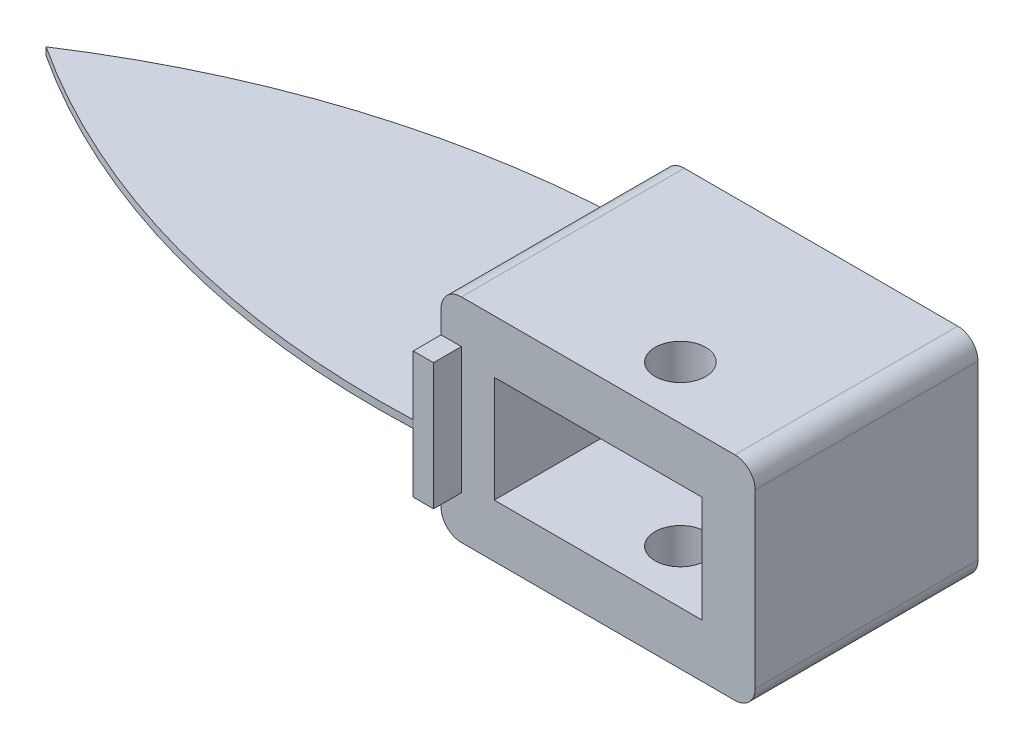
SolidWorks part; units mm, degrees
note: The reader was unsure of these and kept them because the rebuilt part matched: shared geometry of "草圖2<3>", "Sketch2<3>", "草圖5<3>".
ref_plane "前基準面" through (0, 0, 0) normal (0, 0, 1) x (1, 0, 0)
ref_plane "上基準面" through (0, 0, 0) normal (0, 1, 0) x (1, 0, 0)
ref_plane "右基準面" through (0, 0, 0) normal (1, 0, 0) x (0, 0, -1)
sketch "Sketch1" plane through (0, 0, 0) normal (0, 0, 1) x (1, 0, 0)
  line L0 (-29.0958, -4.1361) -> (32.9042, -4.1361) construction
  line L1 (-18.5958, 6.3639) -> (22.4042, 6.3639)
  line L2 (-18.5958, 6.3639) -> (-18.5958, -14.6361)
  line L3 (-18.5958, -14.6361) -> (22.4042, -14.6361)
  line L4 (22.4042, 6.3639) -> (22.4042, -14.6361)
  line L5 (-29.0958, 16.8639) -> (32.9042, 16.8639)
  line L6 (-29.0958, 16.8639) -> (-29.0958, -25.1361)
  line L7 (-29.0958, -25.1361) -> (32.9042, -25.1361)
  line L8 (32.9042, 16.8639) -> (32.9042, -25.1361)
  line L9 (1.9042, 16.8639) -> (1.9042, -25.1361) construction
  line L10 (22.4042, -4.1361) -> (-18.5958, -4.1361) construction
  line L11 (1.9042, 6.3639) -> (1.9042, -14.6361) construction
  point P16 (1.9042, -4.1361)
  point P17 (1.9042, -4.1361)
  dimension "D1" = 21
  dimension "D2" = 41
  dimension "D3" = 62
  dimension "D4" = 42
extrude "Boss-Extrude1" add sketch "Sketch1" along normal blind 43
sketch "Sketch2" plane through (0, 0, 43) normal (0, 0, 1) x (1, 0, 0)
  line L0 (-18.5958, -4.1361) -> (-29.0958, -4.1361) construction
  line L1 (-25.0958, -4.1361) -> (-29.0958, -4.1361) construction
  line L3 (-29.0958, 16.8639) -> (-29.0958, -25.1361) construction
  line L4 (-18.5958, 6.3639) -> (-18.5958, -14.6361) construction
  line L5 (-29.0958, 8.3639) -> (-25.0958, 8.3639)
  line L6 (-29.0958, 8.3639) -> (-29.0958, -16.6361)
  line L7 (-29.0958, -16.6361) -> (-25.0958, -16.6361)
  line L8 (-25.0958, 8.3639) -> (-25.0958, -16.6361)
  dimension "D1" = 25
  dimension "D2" = 4
extrude "Boss-Extrude2" add sketch "Sketch2" along normal blind 5.5
sketch "草圖1" plane through (0, 16.8639, 0) normal (0, 1, 0) x (1, 0, 0)
  circle A1 centre (7.6538, -32.5004) radius 5
  dimension "D1" = 10
extrude "除料-伸長1" cut sketch "草圖1" against normal blind 42
sketch "草圖2" plane through (0, 0, 0) normal (0, 0, -1) x (-1, 0, 0)
  line L0 (-22.4042, -14.6361) -> (-22.4042, 6.3639)
  line L1 (-22.4042, 6.3639) -> (18.5958, 6.3639)
  line L2 (18.5958, 6.3639) -> (18.5958, -14.6361)
  line L3 (18.5958, -14.6361) -> (-22.4042, -14.6361)
  line L4 (18.5958, -4.1361) -> (-22.4042, -4.1361) construction
  line L6 (29.0958, 16.8639) -> (29.0958, -25.1361)
  line L7 (29.0958, -25.1361) -> (-32.9042, -25.1361) construction
  line L8 (29.0958, 16.8639) -> (29.0958, -25.1361) construction
  line L9 (29.0958, -25.1361) -> (-32.9042, -25.1361)
  line L10 (-32.9042, -25.1361) -> (-32.9042, 16.8639)
  line L11 (-32.9042, 16.8639) -> (29.0958, 16.8639) construction
  line L12 (-32.9042, -25.1361) -> (-32.9042, 16.8639) construction
  line L13 (-32.9042, 16.8639) -> (29.0958, 16.8639)
  circle A0 centre (-12.4042, -4.1361) radius 7
  line M14 (18.5958, 6.3639) -> (18.5958, -14.6361)
  line M15 (18.5958, -14.6361) -> (-22.4042, -14.6361)
  line M16 (-22.4042, -14.6361) -> (-22.4042, 6.3639)
  line M17 (-22.4042, 6.3639) -> (18.5958, 6.3639)
  dimension "D1" = 14
  dimension "D2" = 10
extrude "填料-伸長1" add sketch "草圖2" against normal blind 1 contours L4 L0 A0 M14 M17 | L2 L4 A0 M16 M15
extrude "填料-伸長2" add sketch "草圖2<3>" along normal blind 1
sketch "草圖2<3>" plane through (0, 0, 0) normal (0, 0, -1) x (-1, 0, 0) same geometry as "草圖2"
fillet "圓角1" radius 4 1 edges at (32.9042, -25.1361, 21)
fillet "圓角2" radius 4 1 edges at (-29.0958, -25.1361, 21)
fillet "圓角3" radius 4 1 edges at (32.9042, 16.8639, 21)
fillet "圓角4" radius 4 1 edges at (-29.0958, 16.8639, 21)
extrude "填料-伸長3" add sketch "Sketch2<3>" against normal blind 49.5
sketch "Sketch2<3>" plane through (0, 0, 43) normal (0, 0, 1) x (1, 0, 0) same geometry as "Sketch2"
ref_plane "平面1" through (0, -4.1361, 0) normal (0, 1, 0) x (1, 0, 0)
sketch "草圖5" plane through (0, -4.1361, 0) normal (0, 1, 0) x (1, 0, 0)
  line L0 (-29.0958, 6.5) -> (-29.0958, -48.5)
  line L1 (-29.0958, -21) -> (-129.0958, -21)
  arc A0 (-29.0958, 6.5) -> (-129.0958, -21) centre (-36.1676, -163.3529) ccw
  arc A1 (-129.0958, -21) -> (-29.0958, -48.5) centre (-36.1676, 121.3529) ccw
extrude "填料-伸長4" add sketch "草圖5" along normal blind 0.75 contours L0 A0 L1 | L1 A1 L0
extrude "填料-伸長5" add sketch "草圖5<3>" against normal blind 0.75 contours L0 A0 L1 | L1 A1 L0
sketch "草圖5<3>" plane through (0, -4.1361, 0) normal (0, 1, 0) x (1, 0, 0) same geometry as "草圖5"
